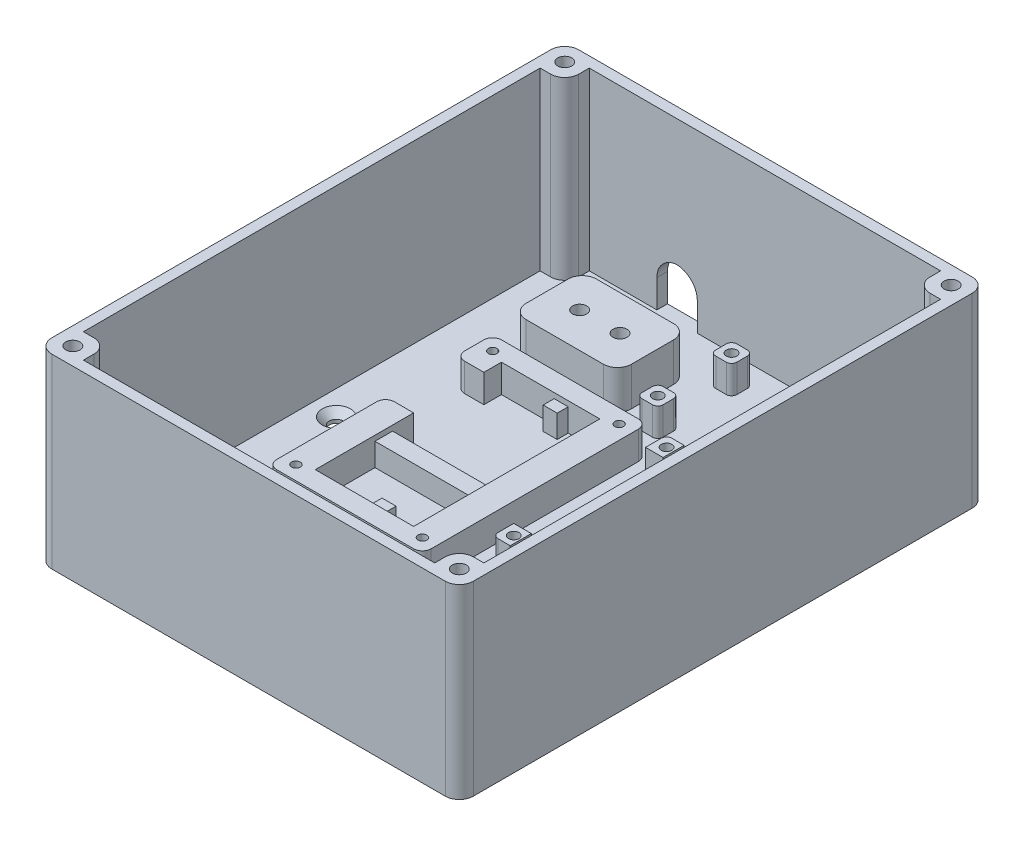
SolidWorks part; units mm, degrees
ref_plane "Alzado" through (0, 0, 0) normal (0, 0, 1) x (1, 0, 0)
ref_plane "Planta" through (0, 0, 0) normal (0, 1, 0) x (1, 0, 0)
ref_plane "Vista lateral" through (0, 0, 0) normal (1, 0, 0) x (0, 0, -1)
sketch "Croquis1" plane through (0, 0, 0) normal (0, 1, 0) x (1, 0, 0)
  line L0 (-60, 0) -> (60, 0) construction
  line L1 (-60, 75) -> (60, 75)
  line L2 (-60, 75) -> (-60, -75)
  line L3 (-60, -75) -> (60, -75)
  line L4 (60, 75) -> (60, -75)
  line L5 (-60, 75) -> (60, -75) construction
  line L6 (-60, -75) -> (60, 75) construction
  circle A2 centre (-50, 0) radius 2
  circle A3 centre (50, 0) radius 2
  point P1 (0, 0)
  dimension "D3" = 4
  dimension "D4" = 10
  dimension "D1" = 120
  dimension "D2" = 150
  dimension "D5" = 10
extrude "Saliente-Extruir1" add sketch "Croquis1" along normal blind 3
sketch "Croquis5" plane through (0, 3, 0) normal (0, 1, 0) x (1, 0, 0)
  line L0 (60, 75) -> (-60, 75) construction
  line L1 (-40, 40) -> (-10, 40)
  line L2 (-40, 40) -> (-40, 60)
  line L3 (-40, 60) -> (-10, 60)
  line L4 (-10, 40) -> (-10, 60)
  line L5 (-40, 40) -> (-10, 60) construction
  line L6 (-40, 60) -> (-10, 40) construction
  line L7 (-60, 75) -> (-60, -75) construction
  line L8 (-30.75, 50) -> (-25, 50) construction
  line L9 (-25, 50) -> (-19.25, 50) construction
  circle A0 centre (-30.75, 50) radius 2
  circle A1 centre (-19.25, 50) radius 2
  point P0 (-25, 50)
  dimension "D5" = 4
  dimension "D1" = 30
  dimension "D2" = 20
  dimension "D3" = 15
  dimension "D4" = 20
  dimension "D6" = 11.5
sketch "Croquis7" plane through (0, 3, 0) normal (0, 1, 0) x (1, 0, 0)
  line L0 (-60, 75) -> (-60, -75) construction
  line L1 (-30, -65) -> (-10, -65)
  line L2 (-30, -65) -> (-30, -35)
  line L3 (-30, -35) -> (-10, -35)
  line L4 (-10, -65) -> (-10, -35)
  line L5 (-30, -65) -> (-10, -35) construction
  line L6 (-30, -35) -> (-10, -65) construction
  line L7 (-60, -75) -> (60, -75) construction
  line L8 (-20, -44.25) -> (-20, -50) construction
  line L9 (-20, -50) -> (-20, -55.75) construction
  circle A0 centre (-20, -44.25) radius 2
  circle A1 centre (-20, -55.75) radius 2
  point P0 (-20, -50)
  dimension "D5" = 4
  dimension "D1" = 30
  dimension "D2" = 20
  dimension "D3" = 30
  dimension "D4" = 10
  dimension "D6" = 11.5
sketch "Croquis4" plane through (0, 3, 0) normal (0, 1, 0) x (1, 0, 0)
  line L1 (-40, -29.5) -> (4, -29.5)
  line L2 (-40, -29.5) -> (-40, 34.5)
  line L3 (-40, 34.5) -> (4, 34.5)
  line L4 (4, -29.5) -> (4, 34.5)
  line L5 (-40, -29.5) -> (4, 34.5) construction
  line L6 (-40, 34.5) -> (4, -29.5) construction
  line L7 (-40, 40) -> (-40, 60) construction
  line L8 (-40, 34.5) -> (-40, 40) construction
  line L9 (-30, -35) -> (-30, -29.5) construction
  circle A0 centre (-36, 30.5) radius 1.25
  circle A1 centre (0, 30.5) radius 1.25
  circle A2 centre (0, -25.5) radius 1.25
  circle A3 centre (-36, -25.5) radius 1.25
  point P0 (-18, 2.5)
  dimension "D3" = 2.5
  dimension "D1" = 64
  dimension "D2" = 44
  dimension "D4" = 4
  dimension "D5" = 4
  dimension "D6" = 4
  dimension "D7" = 4
sketch "Croquis3" plane through (0, 3, 0) normal (0, 1, 0) x (1, 0, 0)
  line L0 (-40, 40) -> (-10, 40) construction
  line L1 (-4.5, 40) -> (30.5, 40) construction
  line L2 (-4.5, 40) -> (-4.5, 67) construction
  line L3 (-4.5, 67) -> (30.5, 67) construction
  line L4 (30.5, 40) -> (30.5, 67) construction
  line L5 (-4.5, 40) -> (30.5, 67) construction
  line L6 (-4.5, 67) -> (30.5, 40) construction
  line L8 (-4.5, 40) -> (-10, 40) construction
  line L9 (-40, 34.5) -> (-40, 40) construction
  line L11 (1.5, 61) -> (-4.5, 61)
  line L12 (1.5, 61) -> (1.5, 67)
  line L13 (1.5, 67) -> (-4.5, 67)
  line L14 (-4.5, 61) -> (-4.5, 67)
  line L15 (1.5, 61) -> (-4.5, 67) construction
  line L16 (1.5, 67) -> (-4.5, 61) construction
  line L17 (24.5, 61) -> (30.5, 61)
  line L18 (24.5, 61) -> (24.5, 67)
  line L19 (24.5, 67) -> (30.5, 67)
  line L20 (30.5, 61) -> (30.5, 67)
  line L21 (24.5, 61) -> (30.5, 67) construction
  line L22 (24.5, 67) -> (30.5, 61) construction
  line L23 (24.5, 46) -> (30.5, 46)
  line L24 (24.5, 46) -> (24.5, 40)
  line L25 (24.5, 40) -> (30.5, 40)
  line L26 (30.5, 46) -> (30.5, 40)
  line L27 (24.5, 46) -> (30.5, 40) construction
  line L28 (24.5, 40) -> (30.5, 46) construction
  line L29 (1.5, 46) -> (-4.5, 46)
  line L30 (1.5, 46) -> (1.5, 40)
  line L31 (1.5, 40) -> (-4.5, 40)
  line L32 (-4.5, 46) -> (-4.5, 40)
  line L33 (1.5, 46) -> (-4.5, 40) construction
  line L34 (1.5, 40) -> (-4.5, 46) construction
  circle A0 centre (-1.5, 64) radius 1.5
  circle A1 centre (27.5, 64) radius 1.5
  circle A2 centre (27.5, 43) radius 1.5
  circle A3 centre (-1.5, 43) radius 1.5
  point P0 (13, 53.5)
  dimension "D5" = 3
  dimension "D1" = 35
  dimension "D2" = 27
  dimension "D3" = 29
  dimension "D4" = 21
sketch "Croquis2" plane through (0, 3, 0) normal (0, 1, 0) x (1, 0, 0)
  line L0 (-40, 34.5) -> (4, 34.5) construction
  line L1 (9.5, -15) -> (36.5, -15) construction
  line L2 (9.5, -15) -> (9.5, 34.5) construction
  line L3 (9.5, 34.5) -> (36.5, 34.5) construction
  line L4 (36.5, -15) -> (36.5, 34.5) construction
  line L5 (9.5, -15) -> (36.5, 34.5) construction
  line L6 (9.5, 34.5) -> (36.5, -15) construction
  line L7 (9.5, 34.5) -> (4, 34.5) construction
  line L8 (-4.5, 40) -> (-10, 40) construction
  line L9 (12.5, 31.5) -> (12.5, 34.5) construction
  line L10 (12.5, 31.5) -> (9.5, 31.5) construction
  line L11 (33.5, 31.5) -> (36.5, 31.5) construction
  line L13 (9.5, 34.5) -> (14.5, 34.5)
  line L14 (9.5, 34.5) -> (9.5, 28.5)
  line L15 (9.5, 28.5) -> (14.5, 28.5)
  line L16 (14.5, 34.5) -> (14.5, 28.5)
  line L17 (36.5, 34.5) -> (31.5, 34.5)
  line L18 (36.5, 34.5) -> (36.5, 28.5)
  line L19 (36.5, 28.5) -> (31.5, 28.5)
  line L20 (31.5, 34.5) -> (31.5, 28.5)
  line L21 (36.5, -15) -> (31.5, -15)
  line L22 (36.5, -15) -> (36.5, -9)
  line L23 (36.5, -9) -> (31.5, -9)
  line L24 (31.5, -15) -> (31.5, -9)
  line L25 (9.5, -15) -> (14.5, -15)
  line L26 (9.5, -15) -> (9.5, -9)
  line L27 (9.5, -9) -> (14.5, -9)
  line L28 (14.5, -15) -> (14.5, -9)
  circle A0 centre (12.5, 31.5) radius 1.5
  circle A1 centre (33.5, 31.5) radius 1.5
  circle A2 centre (33.5, -12) radius 1.5
  circle A3 centre (12.5, -12) radius 1.5
  point P0 (23, 9.75)
  dimension "D5" = 3
  dimension "D1" = 49.5
  dimension "D2" = 27
  dimension "D3" = 43.5
  dimension "D4" = 21
  dimension "D6" = 6
  dimension "D7" = 5
  dimension "D8" = 6
  dimension "D9" = 5
extrude "Saliente-Extruir2" add sketch "Croquis5" along normal blind 11
extrude "Saliente-Extruir3" add sketch "Croquis7" along normal blind 11
extrude "Saliente-Extruir4" add sketch "Croquis3" along normal blind 8
extrude "Saliente-Extruir5" add sketch "Croquis2" along normal blind 8
extrude "Saliente-Extruir6" add sketch "Croquis4" along normal blind 8
sketch "Croquis8" plane through (0, 11, 0) normal (0, 1, 0) x (1, 0, 0)
  line L0 (-32, 29) -> (-32, 34.5) construction
  line L1 (-32, -24) -> (-4, -24)
  line L2 (-32, -24) -> (-32, 29)
  line L3 (-32, 29) -> (-4, 29)
  line L4 (-4, -24) -> (-4, 29)
  line L5 (-32, -24) -> (-4, 29) construction
  line L6 (-32, 29) -> (-4, -24) construction
  line L7 (4, 34.5) -> (-40, 34.5) construction
  line L8 (-32, 29) -> (-40, 29) construction
  line L9 (-40, 34.5) -> (-40, -29.5) construction
  line L10 (-4, 29) -> (4, 29) construction
  line L11 (4, -29.5) -> (4, 34.5) construction
  line L12 (-32, -24) -> (-32, -29.5) construction
  line L13 (-40, -29.5) -> (4, -29.5) construction
  point P0 (-18, 2.5)
  dimension "D1" = 53
  dimension "D2" = 28
extrude "Cortar-Extruir1" cut sketch "Croquis8" against normal blind 1.5
sketch "Croquis9" plane through (0, 9.5, 0) normal (0, 1, 0) x (1, 0, 0)
  line L1 (-32, 29) -> (-17, 29)
  line L2 (-4, 29) -> (-32, 29) construction
  line L3 (-17, 29) -> (-17, 25.8618)
  line L4 (-17, 25.8618) -> (-13, 25.8618)
  line L5 (-13, 25.8618) -> (-13, 29)
  line L6 (-4, 29) -> (-32, 29) construction
  line L7 (-13, 29) -> (-4, 29)
  line L8 (-4, 29) -> (-4, -2)
  line L9 (-4, -24) -> (-4, 29) construction
  line L10 (-4, -2) -> (-32, -2)
  line L11 (-32, 29) -> (-32, -24) construction
  line L12 (-32, -2) -> (-32, 29)
  line L13 (-32, -24) -> (-17, -24)
  line L14 (-32, -24) -> (-4, -24) construction
  line L15 (-17, -24) -> (-17, -20)
  line L16 (-17, -20) -> (-13, -20)
  line L17 (-13, -20) -> (-13, -24)
  line L18 (-13, -24) -> (-4, -24)
  line L19 (-4, -24) -> (-4, -7)
  line L20 (-4, -24) -> (-4, 29) construction
  line L21 (-4, -7) -> (-32, -7)
  line L22 (-32, -7) -> (-32, -24)
  dimension "D1" = 5
  dimension "D2" = 4
  dimension "D3" = 4
  dimension "D4" = 15
  dimension "D5" = 17
  dimension "D6" = 3.1382
extrude "Cortar-Extruir2" cut sketch "Croquis9" against normal up to surface (6.5 mm away) up to face at (-18, 3, -2.5)
sketch "Croquis10" plane through (0, 11, 0) normal (0, 1, 0) x (1, 0, 0)
  line L0 (-32, -2) -> (-32, 29) construction
  line L1 (-32, 24) -> (-40, 24)
  line L2 (-32, 24) -> (-32, 4)
  line L3 (-32, 4) -> (-40, 4)
  line L4 (-40, 24) -> (-40, 4)
  line L5 (-40, 34.5) -> (-40, -29.5) construction
  line L6 (-4, 29) -> (-32, 29) construction
  dimension "D1" = 5
  dimension "D2" = 20
extrude "Cortar-Extruir3" cut sketch "Croquis10" against normal up to surface (8 mm away) up to face at (-18, 3, -2.5)
fillet "Redondeo3" radius 4 8 edges at (-40, 8.5, -40) (-40, 8.5, -60) (-10, 8.5, -40) (-10, 8.5, -60) (-10, 8.5, 35) (-10, 8.5, 65) (-30, 8.5, 65) (-30, 8.5, 35)
fillet "Redondeo4" radius 2.5 6 edges at (4, 7, -34.5) (4, 7, 29.5) (-40, 7, -24) (-40, 7, -4) (-40, 7, -34.5) (-40, 7, 29.5)
fillet "Redondeo5" radius 1.5 20 edges at (36.5, 7, 15) (9.5, 7, 15) (9.5, 7, -34.5) (36.5, 7, -34.5) (24.5, 7, -46) (30.5, 7, -40) (30.5, 7, -46) (24.5, 7, -40) (-4.5, 7, -61) (1.5, 7, -40) (24.5, 7, -61) (1.5, 7, -61) (30.5, 7, -61) (-4.5, 7, -40) (30.5, 7, -67) (24.5, 7, -67) (-4.5, 7, -67) (1.5, 7, -67) (-4.5, 7, -46) (1.5, 7, -46)
sketch "Croquis11" plane through (0, 3, 0) normal (0, 1, 0) x (1, 0, 0)
  line L0 (-60, 75) -> (-60, -75)
  line L1 (-60, -75) -> (60, -75)
  line L2 (60, -75) -> (60, 75)
  line L3 (60, 75) -> (-60, 75)
  line L4 (-50, 72) -> (-50, 65)
  line L5 (-50, 65) -> (-57, 65)
  line L6 (-57, 65) -> (-57, -65)
  line L7 (-57, -65) -> (-50, -65)
  line L8 (-50, -65) -> (-50, -72)
  line L9 (-50, -72) -> (50, -72)
  line L10 (50, -72) -> (50, -65)
  line L11 (50, -65) -> (57, -65)
  line L12 (57, -65) -> (57, 65)
  line L13 (57, 65) -> (50, 65)
  line L14 (50, 65) -> (50, 72)
  line L15 (50, 72) -> (-50, 72)
  point P18 (-53.5, 65)
  dimension "D1" = 3
  dimension "D2" = 3
  dimension "D3" = 3
  dimension "D4" = 10
  dimension "D5" = 10
  dimension "D6" = 10
  dimension "D7" = 3
  dimension "D8" = 10
extrude "Saliente-Extruir7" add sketch "Croquis11" along normal blind 50
sketch "Croquis12" plane through (0, 53, 0) normal (0, 1, 0) x (1, 0, 0)
  line L1 (-60, 75) -> (-50, 75) construction
  line L2 (-60, 75) -> (-60, 65) construction
  line L3 (-60, 65) -> (-50, 65) construction
  line L4 (-50, 75) -> (-50, 65) construction
  line L5 (-60, 75) -> (-50, 65) construction
  line L6 (-60, 65) -> (-50, 75) construction
  line L7 (60, 75) -> (50, 75) construction
  line L8 (60, 75) -> (60, 65) construction
  line L9 (60, 65) -> (50, 65) construction
  line L10 (50, 75) -> (50, 65) construction
  line L11 (60, 75) -> (50, 65) construction
  line L12 (60, 65) -> (50, 75) construction
  line L14 (-60, -75) -> (-50, -75) construction
  line L15 (-60, -75) -> (-60, -65) construction
  line L16 (-60, -65) -> (-50, -65) construction
  line L17 (-50, -75) -> (-50, -65) construction
  line L18 (-60, -75) -> (-50, -65) construction
  line L19 (-60, -65) -> (-50, -75) construction
  line L20 (60, -75) -> (50, -75) construction
  line L21 (60, -75) -> (60, -65) construction
  line L22 (60, -65) -> (50, -65) construction
  line L23 (50, -75) -> (50, -65) construction
  line L24 (60, -75) -> (50, -65) construction
  line L25 (60, -65) -> (50, -75) construction
  circle A0 centre (-55, 70) radius 2
  circle A1 centre (55, 70) radius 2
  circle A2 centre (-55, -70) radius 2
  circle A3 centre (55, -70) radius 2
  point P0 (-55, 70)
  point P6 (55, 70)
  point P15 (-55, -70)
  point P25 (55, -70)
  dimension "D1" = 4
extrude "Cortar-Extruir4" cut sketch "Croquis12" against normal blind 15
chamfer "Chaflán1" distance 2 angle 45 2 edges at (50, 3, 2) (-50, 3, 2)
fillet "Redondeo6" radius 4 4 edges at (-60, 26.5, -75) (60, 26.5, -75) (60, 26.5, 75) (-60, 26.5, 75)
fillet "Redondeo7" radius 4 4 edges at (50, 28, 65) (50, 28, -65) (-50, 28, -65) (-50, 28, 65)
sketch "Croquis13" plane through (-57, 0, 0) normal (1, 0, 0) x (0, 0, -1)
  line L0 (65, 3) -> (-65, 3) construction
  line L1 (-44.25, 3) -> (-55.75, 3)
  line L2 (-44.25, 3) -> (-44.25, 17)
  line L3 (-44.25, 17) -> (-55.75, 17)
  line L4 (-55.75, 3) -> (-55.75, 17)
  dimension "D1" = 14
extrude "Cortar-Extruir5" cut sketch "Croquis13" against normal through all
fillet "Redondeo8" radius 6 2 edges at (-58.5, 17, 55.75) (-58.5, 17, 44.25)
sketch "Croquis16" plane through (0, 0, -72) normal (0, 0, 1) x (1, 0, 0)
  line L0 (50, 3) -> (-50, 3) construction
  line L1 (-30.75, 3) -> (-19.25, 3)
  line L2 (-30.75, 3) -> (-30.75, 17)
  line L3 (-30.75, 17) -> (-19.25, 17)
  line L4 (-19.25, 3) -> (-19.25, 17)
  dimension "D1" = 14
extrude "Cortar-Extruir6" cut sketch "Croquis16" against normal through all
fillet "Redondeo9" radius 6 2 edges at (-30.75, 17, -73.5) (-19.25, 17, -73.5)
